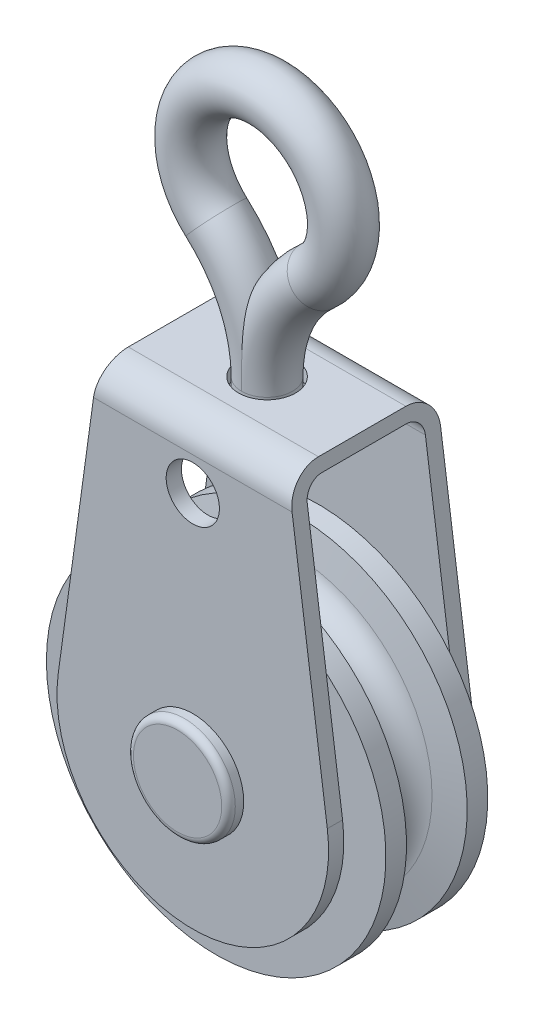
SolidWorks part; units mm, degrees
ref_plane "Front Plane" through (0, 0, 0) normal (0, 0, 1) x (1, 0, 0)
ref_plane "Top Plane" through (0, 0, 0) normal (0, 1, 0) x (1, 0, 0)
ref_plane "Right Plane" through (0, 0, 0) normal (1, 0, 0) x (0, 0, -1)
sketch "Sketch1" plane through (0, 0, 0) normal (0, 0, 1) x (1, 0, 0)
  line L0 (-8.89, 28.575) -> (8.89, 28.575)
  line L1 (0, 0) -> (0, 28.575) construction
  line L2 (-8.89, 28.575) -> (-12.5816, 1.7302)
  line L3 (8.89, 28.575) -> (12.5816, 1.7302)
  line L4 (4.7625, 44.45) -> (9.525, 44.45) construction
  line L5 (-2.3812, 28.575) -> (-2.3812, 40.3256) construction
  line L6 (-2.3812, 28.575) -> (2.3812, 28.575) construction
  line L7 (2.3812, 28.575) -> (2.3812, 40.3256) construction
  circle A0 centre (0, 0) radius 15.875
  arc A1 (-12.5816, 1.7302) -> (12.5816, 1.7302) centre (0, 0) ccw
  circle A2 centre (0, 22.606) radius 2.4892
  circle A3 centre (0, 0) radius 4.7625
  circle A4 centre (0, 44.45) radius 4.7625
  circle A5 centre (0, 44.45) radius 9.525
  arc A6 (-2.3812, 28.575) -> (-6.317, 37.3211) centre (-14.067, 28.575) ccw
  arc A7 (2.3812, 28.575) -> (-3.1585, 40.8856) centre (-14.067, 28.575) ccw
  point P11 (0, 15.875)
  dimension "D1" = 31.75
  dimension "D4" = 25.4
  dimension "D5" = 4.9784
  dimension "D6" = 9.525
  dimension "D10" = 9.525
  dimension "D11" = 19.05
  dimension "D2" = 44.45
  dimension "D3" = 17.78
  dimension "D7" = 22.606
  dimension "D8" = 3.4798
  dimension "D9" = 69.85
  dimension "D12" = 4.7625
  dimension "D13" = 4.7625
sketch "Sketch2" plane through (0, 0, 0) normal (1, 0, 0) x (0, 0, -1)
  line L0 (-2.3451, 13.0803) -> (-2.8379, 15.875)
  line L1 (-4.7625, 15.875) -> (-2.8379, 15.875)
  line L2 (-4.7625, 15.875) -> (-4.7625, 0)
  line L3 (-4.7625, 0) -> (4.7625, 0) construction
  line L4 (4.7625, 15.875) -> (4.7625, 0)
  line L5 (2.3451, 13.0803) -> (2.8379, 15.875)
  line L6 (2.8379, 15.875) -> (4.7625, 15.875)
  line L7 (0, 0) -> (0, 13.4937) construction
  line L8 (4.7625, 0) -> (-4.7625, 0)
  arc A0 (-2.3451, 13.0803) -> (2.3451, 13.0803) centre (0, 13.4937) ccw
  circle A1 centre (0, 13.4937) radius 2.3813 construction
  circle A2 centre (0, -13.4937) radius 2.3812 construction
  dimension "D2" = 4.7625
  dimension "D1" = 9.525
  dimension "D3" = 20
  dimension "D4" = 22.225
revolve "Revolve1" add sketch "Sketch2" angle 360 mid plane about L8
ref_plane "Plane1" through (0, 0, 5.5245) normal (0, 0, 1) x (1, 0, 0)
sketch "Sketch3" plane through (0, 0, 5.5245) normal (0, 0, 1) x (1, 0, 0)
  line L0 (-8.89, 28.575) -> (8.89, 28.575) construction
  line L1 (-8.89, 28.575) -> (-12.5816, 1.7302) construction
  line L2 (8.89, 28.575) -> (12.5816, 1.7302) construction
  line L3 (-8.89, 28.575) -> (8.89, 28.575)
  line L4 (-8.89, 28.575) -> (-12.5816, 1.7302)
  line L5 (8.89, 28.575) -> (12.5816, 1.7302)
  arc A0 (-12.5816, 1.7302) -> (12.5816, 1.7302) centre (0, 0) ccw construction
  circle A1 centre (0, 22.606) radius 2.4892 construction
  arc A2 (-12.5816, 1.7302) -> (12.5816, 1.7302) centre (0, 0) ccw
  circle A3 centre (0, 22.606) radius 2.4892
extrude "Boss-Extrude1" add sketch "Sketch3" along normal blind 1.4224 separate body
sketch "Sketch4" plane through (0, 0, 5.5245) normal (0, 0, -1) x (-1, 0, 0)
  line L0 (-9.0646, 27.305) -> (9.0646, 27.305)
  line L1 (-8.89, 28.575) -> (8.89, 28.575) construction
  line L2 (-12.5816, 1.7302) -> (-8.89, 28.575) construction
  line L3 (8.89, 28.575) -> (12.5816, 1.7302) construction
  line L4 (-8.89, 28.575) -> (8.89, 28.575)
  line L5 (-9.0646, 27.305) -> (-8.89, 28.575)
  line L6 (8.89, 28.575) -> (9.0646, 27.305)
  dimension "D1" = 1.27
extrude "Boss-Extrude2" add sketch "Sketch4" along normal up to surface (5.5245 mm away) up to plane "Front Plane"
fillet "Fillet1" radius 1.5875 1 edges
fillet "Fillet2" radius 2.8575 1 edges at (0, 28.575, 6.9469)
mirror "Mirror1" about plane through (0, 0, 0) normal (0, 0, 1) of bodies 103
sketch "Sketch5" plane through (0, 28.575, 0) normal (0, 1, 0) x (1, 0, 0)
  circle A0 centre (0, 0) radius 2.667
  dimension "D1" = 5.334
extrude "Cut-Extrude1" cut sketch "Sketch5" against normal up to vertex (1.27 mm away) up to point (9.0646, 27.305, -3.937)
sketch "Sketch6" plane through (0, 0, 6.9469) normal (0, 0, 1) x (1, 0, 0)
  circle A0 centre (0, 0) radius 4.7625
  dimension "D1" = 9.525
extrude "Boss-Extrude3" add sketch "Sketch6" along normal blind 1.4224
fillet "Fillet3" radius 0.635 1 edges at (4.7625, 0, 8.3693)
sketch "Sketch7" plane through (0, 0, 5.5245) normal (0, 0, -1) x (-1, 0, 0)
  circle A0 centre (0, 0) radius 2.8575
  dimension "D1" = 5.715
extrude "Boss-Extrude4" add sketch "Sketch7" along normal offset from surface (13.7414 mm away) 1.27 up to face at (0, 10.1163, -6.9469) offset beyond the face yes
sketch "Sketch8" plane through (0, 28.575, 0) normal (0, 1, 0) x (1, 0, 0)
  circle A0 centre (0, 0) radius 2.3812
sketch "Sketch9" plane through (0, 0, 0) normal (0, 0, 1) x (1, 0, 0)
  line L0 (0, 44.45) -> (0, 55.8451) construction
  arc A0 (-2.3812, 28.575) -> (-6.317, 37.3211) centre (-14.067, 28.575) ccw construction
  circle A1 centre (0, 44.45) radius 9.525 construction
  arc A2 (-2.3812, 28.575) -> (-6.317, 37.3211) centre (-14.067, 28.575) ccw
  arc A3 (0, 53.975) -> (-6.317, 37.3211) centre (0, 44.45) ccw
  point P5 (0, 0)
sweep "Sweep1" add profiles "Sketch8" path "Sketch9"
mirror "Mirror3" about plane through (0, 0, 0) normal (1, 0, 0) of "Sweep1"
sketch "Sketch10" plane through (0, 28.575, 0) normal (0, -1, 0) x (1, 0, 0)
  circle A1 centre (0, 0) radius 2.3812
  circle A2 centre (0, 0) radius 2.3812
  dimension "D1" = 0
extrude "Boss-Extrude5" add sketch "Sketch10" along normal blind 1.524
sketch "Sketch11" plane through (0, 27.051, 0) normal (0, -1, 0) x (1, 0, 0)
  circle A0 centre (0, 0) radius 3.9688
  dimension "D1" = 7.9375
extrude "Boss-Extrude6" add sketch "Sketch11" along normal blind 1.778 and the other way blind 0.254
sketch "Sketch12" plane through (0, 0, 0) normal (1, 0, 0) x (0, 0, -1)
  line L0 (0, 44.45) -> (0, 55.8451) construction
  circle A0 centre (0, 51.5938) radius 2.3812 construction
  point P5 (0, 0)
equation "\"D12@Sketch1\" = \"D13@Sketch1\""
